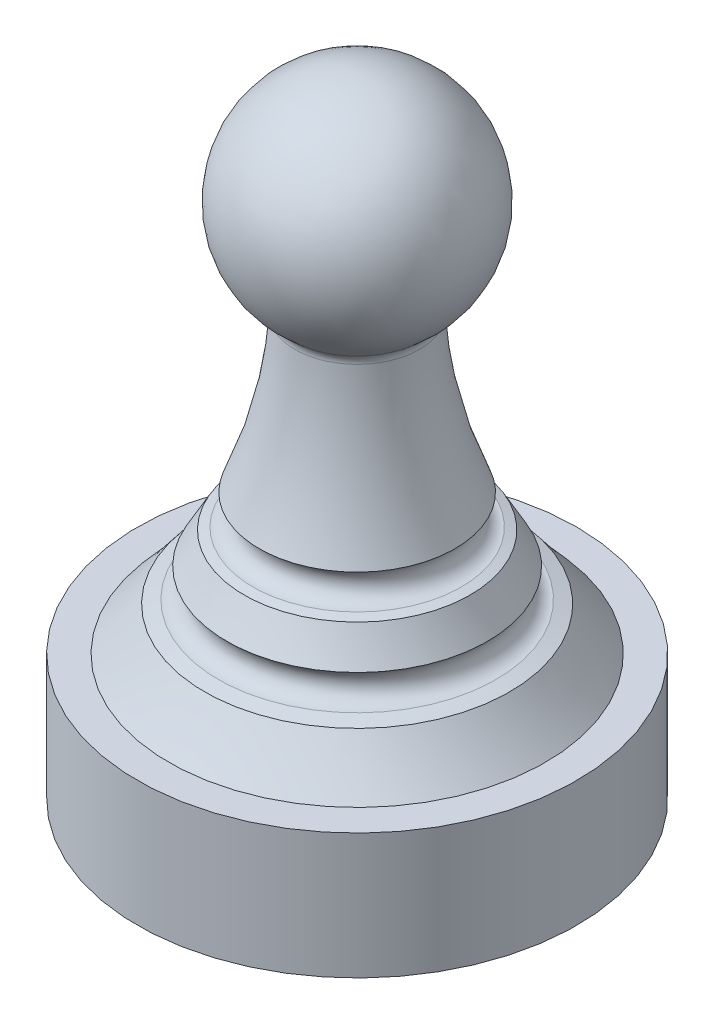
SolidWorks part; units mm, degrees
material "Latão"
ref_plane "Plano frontal" through (0, 0, 0) normal (0, 0, 1) x (1, 0, 0)
ref_plane "Plano superior" through (0, 0, 0) normal (0, 1, 0) x (1, 0, 0)
ref_plane "Plano direito" through (0, 0, 0) normal (1, 0, 0) x (0, 0, -1)
sketch "Esboço1" plane through (0, 0, 0) normal (0, 0, 1) x (1, 0, 0)
  line L0 (-6, 0) -> (0, 0)
  line L2 (-6, 0) -> (-6, 2)
  line L3 (-3.3192, 5.5) -> (-3.6002, 5.4194)
  line L4 (0, 18) -> (0, 0)
  line L5 (0, -3.7998) -> (0, 25.7828) construction
  line L6 (-4.4262, 3.5) -> (-4.8599, 3.3756)
  arc A0 (0, 18) -> (-2.1378, 11.7288) centre (0, 14.5) ccw
  arc A1 (-6, 2) -> (-4.8599, 3.3756) centre (-16.9585, 12.2426) ccw
  arc A2 (-3.1188, 6.458) -> (-1.9828, 11.3893) centre (-16.9585, 12.2426) ccw
  arc A3 (-2.1378, 11.7288) -> (-1.9828, 11.3893) centre (-2.3822, 11.4121) cw
  arc A5 (-4.1584, 4.4223) -> (-3.6002, 5.4194) centre (-16.9585, 12.2426) ccw
  arc A6 (-3.3192, 5.5) -> (-3.1188, 6.458) centre (-3.3192, 6) ccw
  arc A7 (-4.4262, 3.5) -> (-4.1584, 4.4223) centre (-4.4262, 4) ccw
  dimension "D2" = 12
  dimension "D4" = 18
  dimension "D6" = 33.917
  dimension "D7" = 2
  dimension "D8" = 0.1244
  dimension "D9" = 2
  dimension "D3" = 3.5
  dimension "D5" = 15
  dimension "D11" = 1
  dimension "D12" = 1
  dimension "D14" = 0.4
  dimension "D10" = 2
  dimension "D13" = 0.0806
revolve "Revolução1" add sketch "Esboço1" angle 360 about L5
sketch "Sketch3" plane through (0, 0, 0) normal (0, -1, 0) x (1, 0, 0)
  circle A0 centre (0, 0) radius 7
  point P3 (0, 0)
  dimension "D1" = 14
extrude "Boss-Extrude1" add sketch "Sketch3" along normal blind 2 contours A0
extrude "Boss-Extrude2" add sketch "Sketch3<3>" against normal blind 2
sketch "Sketch3<3>" plane through (0, 0, 0) normal (0, -1, 0) x (1, 0, 0) same geometry as "Sketch3"
sketch "Sketch5" plane through (0, -2, 0) normal (0, -1, 0) x (1, 0, 0)
  circle A0 centre (0, 0) radius 6.05
  dimension "D1" = 12.1
extrude "Cut-Extrude1" cut sketch "Sketch5" against normal blind 3.2 contours A0
